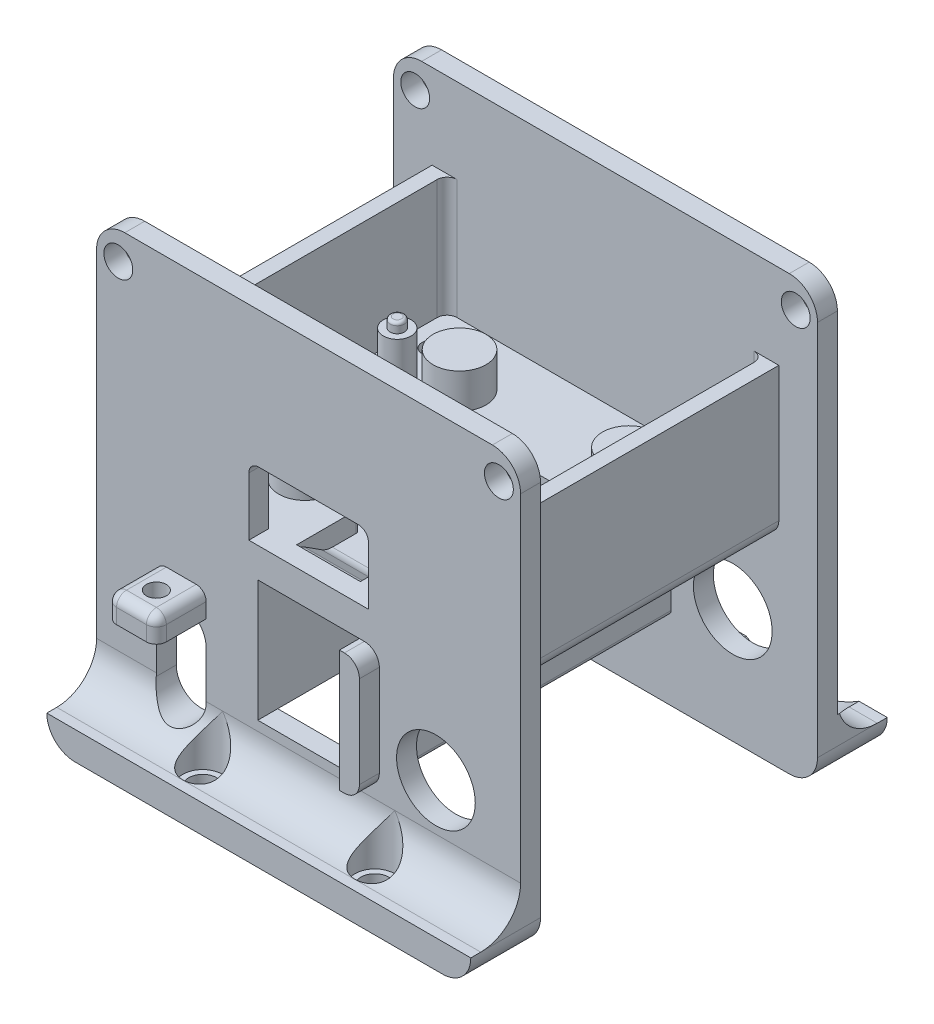
SolidWorks part; units mm, degrees
other "标注1"
sketch "草图55" plane through (-21.28, -20, 20.9) normal (0, 0, 1) x (1, 0, 0)
material "尼龙 101"
ref_plane "前视基准面" through (0, 0, 0) normal (0, 0, 1) x (1, 0, 0)
ref_plane "上视基准面" through (0, 0, 0) normal (0, 1, 0) x (1, 0, 0)
ref_plane "右视基准面" through (0, 0, 0) normal (1, 0, 0) x (0, 0, -1)
other "Configuration Table"
sketch "草图1" plane through (0, 0, 0) normal (0, 1, 0) x (1, 0, 0)
  line L1 (-15.9, 13.9) -> (15.9, 13.9)
  line L2 (-15.9, 13.9) -> (-15.9, -13.9)
  line L3 (-15.9, -13.9) -> (15.9, -13.9)
  line L4 (15.9, 13.9) -> (15.9, -13.9)
  line L5 (-15.9, 13.9) -> (15.9, -13.9) construction
  line L6 (-15.9, -13.9) -> (15.9, 13.9) construction
  point P0 (0, 0)
  dimension "D1" = 31.8
  dimension "D2" = 27.8
extrude "凸台-拉伸1" add sketch "草图1" along normal blind 3
sketch "草图2" plane through (0, 3, 0) normal (0, 1, 0) x (1, 0, 0)
  line L0 (0, 0) -> (0, 5.35) construction
  line L1 (-5.35, 5.35) -> (5.35, 5.35)
  line L2 (5.35, 5.35) -> (5.35, -7.55)
  line L3 (5.35, -7.55) -> (4.35, -7.55)
  line L4 (4.35, -7.55) -> (4.35, 4.35)
  line L5 (4.35, 4.35) -> (-4.35, 4.35)
  line L6 (-4.35, -7.55) -> (-4.35, 4.35)
  line L7 (-5.35, -7.55) -> (-4.35, -7.55)
  line L8 (-5.35, 5.35) -> (-5.35, -7.55)
  point P9 (0, 4.35)
  dimension "D1" = 8.7
  dimension "D2" = 11.9
  dimension "D3" = 4.35
  dimension "D4" = 1
  dimension "D5" = 1
extrude "凸台-拉伸2" add sketch "草图2" along normal blind 1.5
sketch "草图5" plane through (0, 3, 0) normal (0, 1, 0) x (1, 0, 0)
  line L0 (0, 13.9) -> (0, 0) construction
  line L1 (15.9, 13.9) -> (-15.9, 13.9) construction
  line L2 (0, 0) -> (15.9, 0) construction
  line L3 (15.9, -13.9) -> (15.9, 13.9) construction
  circle A0 centre (12.5, 5.5) radius 1.4
  circle A1 centre (12.5, -5.5) radius 1.4
  circle A2 centre (-12.5, -5.5) radius 1.4
  circle A3 centre (-12.5, 5.5) radius 1.4
  dimension "D1" = 2.8
  dimension "D2" = 25
  dimension "D3" = 11
extrude "凸台-拉伸3" add sketch "草图5" along normal blind 4.5
sketch "草图6" plane through (0, 7.5, 0) normal (0, 1, 0) x (1, 0, 0)
  circle A0 centre (-12.5, -5.5) radius 0.725
  circle A1 centre (-12.5, 5.5) radius 0.725
  circle A2 centre (12.5, 5.5) radius 0.725
  circle A3 centre (12.5, -5.5) radius 0.725
  dimension "D1" = 1.45
extrude "凸台-拉伸4" add sketch "草图6" along normal blind 1
sketch "草图7" plane through (0, 3, 0) normal (0, 1, 0) x (1, 0, 0)
  line L0 (0, 0) -> (0, 13.9) construction
  line L1 (15.9, 13.9) -> (-15.9, 13.9) construction
  line L2 (0, 0) -> (15.9, 0) construction
  line L3 (15.9, -13.9) -> (15.9, 13.9) construction
  circle A0 centre (13.5, 10) radius 1
  circle A1 centre (-13.5, 10) radius 1
  circle A2 centre (-13.5, -10) radius 1
  circle A3 centre (13.5, -10) radius 1
  dimension "D1" = 2
  dimension "D2" = 20
  dimension "D3" = 27
extrude "切除-拉伸1" cut sketch "草图7" against normal blind 10
sketch "草图8" plane through (0, 0, 0) normal (0, -1, 0) x (1, 0, 0)
  circle A0 centre (-13.5, 10) radius 2
  circle A1 centre (13.5, 10) radius 2
  circle A2 centre (13.5, -10) radius 2
  circle A3 centre (-13.5, -10) radius 2
  dimension "D1" = 4
extrude "切除-拉伸2" cut sketch "草图8" against normal blind 1
fillet "圆角1" radius 1 4 edges at (-15.9, 1.5, -13.9) (15.9, 1.5, -13.9) (-15.9, 1.5, 13.9) (15.9, 1.5, 13.9)
sketch "草图9" plane through (0, 3, 0) normal (0, 1, 0) x (1, 0, 0)
  line L0 (0, 13.9) -> (0, 0) construction
  line L1 (14.9, 13.9) -> (-14.9, 13.9) construction
  line L2 (0, 0) -> (15.9, 0) construction
  line L3 (15.9, -12.9) -> (15.9, 12.9) construction
  circle A0 centre (8.5, 7.75) radius 2.65
  circle A1 centre (-8.5, 7.75) radius 2.65
  circle A2 centre (-8.5, -7.75) radius 2.65
  circle A3 centre (8.5, -7.75) radius 2.65
  dimension "D1" = 17
  dimension "D2" = 15.5
  dimension "D3" = 5.3
extrude "凸台-拉伸5" add sketch "草图9" along normal blind 3.5
fillet "圆角2" radius 0.3 4 edges at (12.5, 8.5, -4.775) (12.5, 8.5, 6.225) (-12.5, 8.5, 6.225) (-12.5, 8.5, -4.775)
sketch "草图15" plane through (0, 3, 0) normal (0, 1, 0) x (1, 0, 0)
  line L0 (0, 0) -> (0, 13.9) construction
  line L1 (14.9, 13.9) -> (-14.9, 13.9) construction
  line L2 (-4.35, 4.35) -> (4.35, 4.35)
  line L3 (4.35, 4.35) -> (4.35, -7.55)
  line L4 (4.35, -7.55) -> (3.2, -7.55)
  line L5 (3.2, -7.55) -> (3.2, -13.9)
  line L6 (-14.9, -13.9) -> (14.9, -13.9) construction
  line L7 (3.2, -13.9) -> (-3.2, -13.9)
  line L8 (-3.2, -7.55) -> (-3.2, -13.9)
  line L9 (-4.35, -7.55) -> (-3.2, -7.55)
  line L10 (-4.35, 4.35) -> (-4.35, -7.55)
  line L11 (4.35, 4.35) -> (4.35, -7.55) construction
  point P14 (0, -13.9)
  point P17 (0, 4.35)
  dimension "D1" = 6.4
extrude "切除-拉伸8" cut sketch "草图15" against normal blind 2
sketch "草图17" plane through (0, 4.5, 0) normal (0, 1, 0) x (1, 0, 0)
  line L8 (-4.35, -7.55) -> (-4.35, 4.35)
  line L9 (-4.35, 4.35) -> (4.35, 4.35)
  line L10 (4.35, 4.35) -> (4.35, -7.55)
  line L11 (4.35, -7.55) -> (5.35, -7.55)
  line L12 (5.35, -7.55) -> (5.35, 5.35)
  line L13 (5.35, 5.35) -> (-5.35, 5.35)
  line L14 (-5.35, 5.35) -> (-5.35, -7.55)
  line L15 (-5.35, -7.55) -> (-4.35, -7.55)
  line L16 (-4.35, -7.55) -> (-4.35, 4.35)
  line L17 (-4.35, 4.35) -> (4.35, 4.35)
  line L18 (4.35, 4.35) -> (4.35, -7.55)
  line L19 (4.35, -7.55) -> (5.35, -7.55)
  line L20 (5.35, -7.55) -> (5.35, 5.35)
  line L21 (5.35, 5.35) -> (-5.35, 5.35)
  line L22 (-5.35, 5.35) -> (-5.35, -7.55)
  line L23 (-5.35, -7.55) -> (-4.35, -7.55)
  dimension "D1" = 0
extrude "切除-拉伸9" cut sketch "草图17" against normal blind 1.5
sketch "草图18" plane through (3.2, 0, 0) normal (-1, 0, 0) x (0, 0, 1)
  line L0 (13.9, 1) -> (10.9, 1)
  line L2 (13.9, 1) -> (13.9, 3) construction
  line L3 (13.9, 2.6) -> (13.9, 1)
  line L5 (13.9, 3) -> (13.9, 0) construction
  line L6 (13.9, 2.6) -> (13.4, 2.6)
  line L7 (13.4, 2.6) -> (10.9, 1)
  line L8 (13.9, 3) -> (12.9, 3) construction
  dimension "D1" = 3
  dimension "D2" = 0.4
  dimension "D3" = 0.5
extrude "凸台-拉伸6" add sketch "草图18" along normal up to surface (6.4 mm away) up to face at (-3.2, 2, 10.725)
fillet "圆角3" radius 2 1 edges at (0, 1, 10.9)
fillet "圆角5" radius 1 1 edges at (0, 2.6, 13.4)
fillet "圆角6" radius 0.4 2 edges at (3.2, 2, 7.55) (-3.2, 2, 7.55)
sketch "草图21" plane through (0, 0, 0) normal (0, -1, 0) x (1, 0, 0)
  line L0 (-14.9, 13.9) -> (14.9, 13.9) construction
  line L1 (-15.9, -12.9) -> (-15.9, 12.9) construction
  line L2 (14.9, -13.9) -> (-14.9, -13.9) construction
  line L3 (15.9, 12.9) -> (15.9, -12.9) construction
  line L4 (-14.9, 13.9) -> (14.9, 13.9)
  line L5 (-15.9, -12.9) -> (-15.9, 12.9)
  line L6 (14.9, -13.9) -> (-14.9, -13.9)
  line L7 (15.9, 12.9) -> (15.9, -12.9)
  line L9 (-17.4, 15.9) -> (17.4, 15.9)
  line L10 (-17.4, 15.9) -> (-17.4, -15.9)
  line L11 (-17.4, -15.9) -> (17.4, -15.9)
  line L12 (17.4, 15.9) -> (17.4, -15.9)
  arc A0 (15.9, 12.9) -> (14.9, 13.9) centre (14.9, 12.9) ccw construction
  arc A1 (-14.9, 13.9) -> (-15.9, 12.9) centre (-14.9, 12.9) ccw construction
  arc A2 (-15.9, -12.9) -> (-14.9, -13.9) centre (-14.9, -12.9) ccw construction
  arc A3 (14.9, -13.9) -> (15.9, -12.9) centre (14.9, -12.9) ccw construction
  arc A4 (15.9, 12.9) -> (14.9, 13.9) centre (14.9, 12.9) ccw
  arc A5 (-14.9, 13.9) -> (-15.9, 12.9) centre (-14.9, 12.9) ccw
  arc A6 (-15.9, -12.9) -> (-14.9, -13.9) centre (-14.9, -12.9) ccw
  arc A7 (14.9, -13.9) -> (15.9, -12.9) centre (14.9, -12.9) ccw
  dimension "D1" = 1.5
  dimension "D2" = 1.5
  dimension "D3" = 2
  dimension "D4" = 2
extrude "凸台-拉伸7" add sketch "草图21" against normal blind 15
sketch "草图22" plane through (0, 0, 15.9) normal (0, 0, 1) x (1, 0, 0)
  line L2 (-21.28, 0) -> (-21.28, 20.67)
  line L3 (-18.45, 23.5) -> (18.45, 23.5)
  line L4 (21.28, 0) -> (21.28, 20.67)
  line L5 (-21.28, 0) -> (21.28, 23.5) construction
  line L6 (-21.28, 23.5) -> (21.28, 0) construction
  line L7 (0, 0) -> (0, 23.5) construction
  line L10 (-21.28, 0) -> (-21.28, -17.17)
  line L11 (-18.45, -20) -> (18.45, -20)
  line L12 (21.28, 0) -> (21.28, -17.17)
  arc A0 (-21.28, 20.67) -> (-18.45, 23.5) centre (-18.45, 20.67) cw
  arc A1 (18.45, 23.5) -> (21.28, 20.67) centre (18.45, 20.67) cw
  arc A4 (18.45, -20) -> (21.28, -17.17) centre (18.45, -17.17) ccw
  arc A5 (-21.28, -17.17) -> (-18.45, -20) centre (-18.45, -17.17) ccw
  circle A6 centre (-19.1, 20.67) radius 1.45
  circle A7 centre (19.1, 20.67) radius 1.45
  point P4 (0, 11.75)
  point P22 (21.28, -20)
  dimension "D3" = 2.83
  dimension "D4" = 2.83
  dimension "D8" = 2.83
  dimension "D1" = 42.56
  dimension "D2" = 23.5
  dimension "D7" = 20
extrude "凸台-拉伸8" add sketch "草图22" against normal blind 2
sketch "草图24" plane through (0, 0, -15.9) normal (0, 0, -1) x (-1, 0, 0)
  line L5 (-18.45, -20) -> (18.45, -20)
  line L6 (-18.45, -20) -> (18.45, -20)
  line L21 (21.28, -17.17) -> (21.28, 20.67)
  line L22 (18.45, 23.5) -> (-18.45, 23.5)
  line L23 (-21.28, 20.67) -> (-21.28, -17.17)
  line L37 (21.28, -17.17) -> (21.28, 20.67)
  line L38 (18.45, 23.5) -> (-18.45, 23.5)
  line L39 (-21.28, 20.67) -> (-21.28, -17.17)
  arc A2 (21.28, 20.67) -> (18.45, 23.5) centre (18.45, 20.67) ccw
  arc A3 (-18.45, 23.5) -> (-21.28, 20.67) centre (-18.45, 20.67) ccw
  arc A4 (21.28, 20.67) -> (18.45, 23.5) centre (18.45, 20.67) ccw
  arc A5 (-18.45, 23.5) -> (-21.28, 20.67) centre (-18.45, 20.67) ccw
  circle A8 centre (-19.1, 20.67) radius 1.45
  circle A9 centre (19.1, 20.67) radius 1.45
  arc A12 (-21.28, -17.17) -> (-18.45, -20) centre (-18.45, -17.17) ccw
  arc A13 (-21.28, -17.17) -> (-18.45, -20) centre (-18.45, -17.17) ccw
  arc A14 (18.45, -20) -> (21.28, -17.17) centre (18.45, -17.17) ccw
  arc A15 (18.45, -20) -> (21.28, -17.17) centre (18.45, -17.17) ccw
  dimension "D1" = 0
extrude "凸台-拉伸9" add sketch "草图24" against normal blind 2
sketch "草图25" plane through (0, 0, 15.9) normal (0, 0, 1) x (1, 0, 0)
  line L1 (-5, 9.85) -> (5, 9.85)
  line L2 (-6, 8.85) -> (-6, 3)
  line L4 (6, 8.85) -> (6, 3)
  line L5 (-6, 3) -> (6, 3)
  line L9 (-6, 3) -> (6, 9.85) construction
  arc A0 (5, 9.85) -> (6, 8.85) centre (5, 8.85) cw
  arc A1 (-5, 9.85) -> (-6, 8.85) centre (-5, 8.85) ccw
  point P5 (6, 9.85)
  point P8 (0, 6.425)
  point P9 (-6, 9.85)
  dimension "D2" = 1
  dimension "D1" = 12
extrude "切除-拉伸10" cut sketch "草图25" against normal blind 2
sketch "草图27" plane through (0, 0, 15.9) normal (0, 0, 1) x (1, 0, 0)
  line L0 (-5.1, 0) -> (5.1, -12.2) construction
  line L5 (-5.1, 0) -> (5.1, 0) construction
  line L16 (-17.4, 0) -> (17.4, 0) construction
  line L18 (-5.1, 0) -> (-5.1, -12.2)
  line L20 (5.1, 0) -> (5.1, -12.2)
  line L21 (-6.6, 0) -> (-6.6, -11.7)
  line L26 (6.6, 0) -> (6.6, -11.7)
  line L31 (-6.6, 0) -> (-5.1, 0)
  line L33 (-6.1, -12.2) -> (-5.1, -12.2)
  line L34 (-6.6, 1.5) -> (6.6, 1.5) construction
  line L35 (0, 0) -> (0, -4.0507) construction
  line L36 (6.6, 1.5) -> (6.6, -13.7) construction
  line L37 (-6.6, 1.5) -> (-6.6, -13.7) construction
  line L38 (5.1, 0) -> (6.6, 0)
  line L39 (-6.6, -13.7) -> (6.6, -13.7) construction
  line L40 (-5.1, -12.2) -> (5.1, -12.2) construction
  line L41 (5.1, -12.2) -> (6.1, -12.2)
  arc A4 (6.1, -12.2) -> (6.6, -11.7) centre (6.1, -11.7) ccw
  arc A5 (-6.6, -11.7) -> (-6.1, -12.2) centre (-6.1, -11.7) ccw
  point P6 (-2.5, 0)
  point P7 (6.9808, -17.5163)
  point P19 (6.6, -12.2)
  point P24 (0, -6.1)
  dimension "D4" = 0.5
  dimension "D1" = 10.2
  dimension "D2" = 12.2
  dimension "D3" = 1.5
extrude "凸台-拉伸10" add sketch "草图27" against normal up to surface (29.8 mm away) up to face at (0, 8.25, -13.9)
sketch "草图35" plane through (0, 0, 15.9) normal (0, 0, 1) x (1, 0, 0)
  line L1 (-5.1, 0) -> (5.1, 0)
  line L2 (-5.1, 0) -> (-5.1, -12.2)
  line L3 (-5.1, -12.2) -> (5.1, -12.2)
  line L4 (5.1, 0) -> (5.1, -12.2)
extrude "切除-拉伸14" cut sketch "草图35" against normal through all
sketch "草图43" plane through (0, 0, 15.9) normal (0, 0, 1) x (1, 0, 0)
  line L0 (-21.28, -17.17) -> (21.28, -17.17)
  line L1 (-18.45, -20) -> (18.45, -20) construction
  line L2 (-18.45, -20) -> (18.45, -20)
  arc A1 (18.45, -20) -> (21.28, -17.17) centre (18.45, -17.17) ccw construction
  arc A3 (-21.28, -17.17) -> (-18.45, -20) centre (-18.45, -17.17) ccw construction
  arc A4 (18.45, -20) -> (21.28, -17.17) centre (18.45, -17.17) ccw
  arc A5 (-21.28, -17.17) -> (-18.45, -20) centre (-18.45, -17.17) ccw
extrude "凸台-拉伸14" add sketch "草图43" along normal blind 5
sketch "草图44" plane through (-21.28, 0, 0) normal (-1, 0, 0) x (0, 0, 1)
  line L3 (15.9, -13.17) -> (15.9, -17.17)
  line L4 (15.9, -17.17) -> (19.9, -17.17)
  arc A0 (19.9, -17.17) -> (15.9, -13.17) centre (19.9, -13.17) cw
  point P8 (15.9, -17.17)
  dimension "D1" = 4
extrude "凸台-拉伸15" add sketch "草图44" against normal up to surface (42.56 mm away) up to face at (21.28, 1.75, 14.9)
sketch "草图45" plane through (0, 0, -15.9) normal (0, 0, -1) x (-1, 0, 0)
  line L0 (-18.45, -20) -> (18.45, -20) construction
  line L1 (-21.28, -17.17) -> (21.28, -17.17) construction
  line L2 (-18.45, -20) -> (18.45, -20)
  line L3 (-21.28, -17.17) -> (21.28, -17.17)
  arc A0 (-21.28, -17.17) -> (-18.45, -20) centre (-18.45, -17.17) ccw construction
  arc A1 (18.45, -20) -> (21.28, -17.17) centre (18.45, -17.17) ccw construction
  arc A2 (-21.28, -17.17) -> (-18.45, -20) centre (-18.45, -17.17) ccw
  arc A3 (18.45, -20) -> (21.28, -17.17) centre (18.45, -17.17) ccw
extrude "凸台-拉伸16" add sketch "草图45" along normal blind 5
sketch "草图46" plane through (21.28, 0, 0) normal (1, 0, 0) x (0, 0, -1)
  line L0 (15.9, -13.17) -> (15.9, -17.17)
  line L1 (15.9, -17.17) -> (19.9, -17.17)
  arc A0 (15.9, -13.17) -> (19.9, -17.17) centre (19.9, -13.17) ccw
  point P7 (15.9, -17.17)
  dimension "D1" = 4
extrude "凸台-拉伸17" add sketch "草图46" against normal up to surface (42.56 mm away) up to face at (-21.28, 1.75, -14.9)
sketch "草图36" plane through (0, 0, 15.9) normal (0, 0, 1) x (1, 0, 0)
  line L0 (-5.1, 0) -> (5.1, -12.2) construction
  line L1 (5.1, 0) -> (-5.1, -12.2) construction
  line L2 (-5.1, -12.2) -> (5.1, -12.2) construction
  line L3 (-5.1, 0) -> (-5.1, -12.2) construction
  line L6 (-5.1, -12.2) -> (-5.1, -13.2) construction
  line L7 (-5.1, -13.2) -> (22.8364, -13.2) construction
  line L8 (21.28, -13.17) -> (21.28, 20.67) construction
  line L10 (-15.28, -8.4815) -> (-15.28, -13.4815)
  line L12 (-10.28, -13.4815) -> (-10.28, -8.4815)
  circle A0 centre (0, -6.1) radius 4.5 construction
  circle A3 centre (12.78, -8.4815) radius 8.5 construction
  circle A6 centre (12.78, -8.4815) radius 5.75 construction
  circle A7 centre (12.78, -8.4815) radius 3.95
  arc A9 (-10.28, -8.4815) -> (-15.28, -8.4815) centre (-12.78, -8.4815) ccw
  arc A11 (-15.28, -13.4815) -> (-10.28, -13.4815) centre (-12.78, -13.4815) ccw
  point P11 (0, -6.1)
  dimension "D1" = 9
  dimension "D2" = 17
  dimension "D3" = 7.9
  dimension "D4" = 9
  dimension "D5" = 11.5
extrude "切除-拉伸15" cut sketch "草图36" against normal through all both and the other way through all
sketch "草图37" plane through (0, 0, 15.9) normal (0, 0, 1) x (1, 0, 0)
  line L0 (-15.28, -5.9815) -> (-15.28, -3.4815)
  line L1 (-15.28, -3.4815) -> (-10.28, -3.4815)
  line L2 (-10.28, -3.4815) -> (-10.28, -5.9815)
  line L3 (-15.28, -5.9815) -> (-10.28, -5.9815)
extrude "凸台-拉伸11" add sketch "草图37" along normal blind 5
sketch "草图38" plane through (0, 0, -15.9) normal (0, 0, -1) x (-1, 0, 0)
  line L0 (15.28, -3.4815) -> (15.28, -5.9815) construction
  line L1 (10.28, -5.9815) -> (10.28, -3.4815) construction
  line L2 (10.28, -3.4815) -> (15.28, -3.4815) construction
  line L3 (15.28, -3.4815) -> (15.28, -5.9815)
  line L4 (10.28, -5.9815) -> (10.28, -3.4815)
  line L5 (10.28, -3.4815) -> (15.28, -3.4815)
  line L6 (10.28, -5.9815) -> (15.28, -5.9815)
extrude "凸台-拉伸12" add sketch "草图38" along normal blind 5
fillet "圆角7" radius 1 2 edges at (-10.28, -4.7315, 20.9) (-15.28, -4.7315, 20.9)
fillet "圆角8" radius 1 2 edges at (-10.28, -4.7315, -20.9) (-15.28, -4.7315, -20.9)
sketch "草图41" plane through (0, 0, 15.9) normal (0, 0, 1) x (1, 0, 0)
  line L1 (5.1, 0) -> (5.6, 0)
  line L2 (5.1, 0) -> (5.1, -12.2)
  line L3 (5.1, -12.2) -> (5.6, -12.2)
  line L4 (7.1, -1.5) -> (7.1, -10.7)
  arc A0 (5.6, -12.2) -> (7.1, -10.7) centre (5.6, -10.7) ccw
  arc A1 (7.1, -1.5) -> (5.6, 0) centre (5.6, -1.5) ccw
  dimension "D1" = 1.5
  dimension "D2" = 2
extrude "凸台-拉伸13" add sketch "草图41" along normal blind 2
sketch "草图42" plane through (0, -3.4815, 0) normal (0, 1, 0) x (1, 0, 0)
  line L0 (-14.9871, 20.6071) -> (-10.28, 15.9) construction
  line L1 (-15.28, -15.9) -> (-10.5729, -20.6071) construction
  line L2 (-10.5729, 20.6071) -> (-15.28, 15.9) construction
  line L3 (-10.28, -15.9) -> (-14.9871, -20.6071) construction
  arc A0 (-14.28, 20.9) -> (-15.28, 19.9) centre (-14.28, 19.9) ccw construction
  arc A1 (-10.28, 19.9) -> (-11.28, 20.9) centre (-11.28, 19.9) ccw construction
  arc A2 (-11.28, -20.9) -> (-10.28, -19.9) centre (-11.28, -19.9) ccw construction
  arc A3 (-15.28, -19.9) -> (-14.28, -20.9) centre (-14.28, -19.9) ccw construction
  circle A4 centre (-12.78, -18.4) radius 1
  circle A5 centre (-12.78, 18.4) radius 1
  point P24 (-12.78, 18.4)
  point P25 (-12.78, -18.4)
  dimension "D1" = 2
  dimension "D2" = 2
sketch "草图49" plane through (0, -20, 0) normal (0, -1, 0) x (1, 0, 0)
  line L5 (8.64, 17.89) -> (-8.64, -17.89) construction
  line L6 (-8.64, 17.89) -> (8.64, 17.89) construction
  line L7 (-8.64, 17.89) -> (-8.64, -17.89) construction
  line L8 (-8.64, -17.89) -> (8.64, -17.89) construction
  line L9 (8.64, 17.89) -> (8.64, -17.89) construction
  circle A1 centre (-8.64, 17.89) radius 1.4
  circle A2 centre (8.64, 17.89) radius 1.4
  circle A3 centre (8.64, -17.89) radius 1.4
  circle A4 centre (-8.64, -17.89) radius 1.4
  point P6 (0, 0)
  dimension "D1" = 17.28
  dimension "D2" = 35.78
extrude "切除-拉伸17" cut sketch "草图49" against normal blind 6
sketch "草图51" plane through (0, 0, -15.9) normal (0, 0, -1) x (-1, 0, 0)
  circle A3 centre (-12.78, -8.4815) radius 10.3764
extrude "切除-拉伸18" cut sketch "草图51" along normal blind 6
sketch "草图52" plane through (0, -17.17, 0) normal (0, 1, 0) x (1, 0, 0)
  circle A3 centre (-8.64, -17.89) radius 1.99
  circle A4 centre (-8.64, 17.89) radius 1.99
  circle A5 centre (8.64, 17.89) radius 1.99
  circle A6 centre (8.64, -17.89) radius 1.99
extrude "切除-拉伸19" cut sketch "草图52" against normal blind 1.5
extrude "切除-拉伸20" cut sketch "草图52<2>" along normal blind 4
sketch "草图52<2>" plane through (0, -17.17, 0) normal (0, 1, 0) x (1, 0, 0) same geometry as "草图52"
fillet "圆角10" radius 1 5 edges at (-14.9871, -3.4815, 20.6071) (-12.78, -3.4815, 20.9) (-10.5729, -3.4815, 20.6071) (-10.28, -3.4815, 17.9) (-15.28, -3.4815, 17.9)
fillet "圆角12" radius 1 5 edges at (-15.28, -3.4815, -17.9) (-14.9871, -3.4815, -20.6071) (-12.78, -3.4815, -20.9) (-10.5729, -3.4815, -20.6071) (-10.28, -3.4815, -17.9)
extrude "切除-拉伸21" cut sketch "草图42" against normal blind 4
ref_plane "基准面7" through (0, 0, -6.3) normal (0, 0, -1) x (-1, 0, 0)
sketch "草图54" plane through (0, 0, -6.3) normal (0, 0, -1) x (-1, 0, 0)
  line L0 (-5.1, 0) -> (5.1, -12.2) construction
  line L1 (-5.1, 0) -> (5.1, 0)
  line L2 (-5.1, 0) -> (-5.1, -12.2)
  line L3 (-5.1, -12.2) -> (5.1, -12.2)
  line L4 (5.1, 0) -> (5.1, -12.2)
  line L5 (0, -1.6) -> (0, -10.6) construction
  circle A0 centre (0, -1.6) radius 0.8
  circle A1 centre (0, -10.6) radius 0.8
  circle A2 centre (0, -6.1) radius 1.8
  point P8 (0, -6.1)
  point P11 (0, -6.1)
  dimension "D1" = 9
  dimension "D2" = 0
  dimension "D3" = 0
extrude "凸台-拉伸18" add sketch "草图54" along normal blind 2
fillet "圆角13" radius 1.5 2 edges at (17.4, 0, 0) (-17.4, 0, 0)
